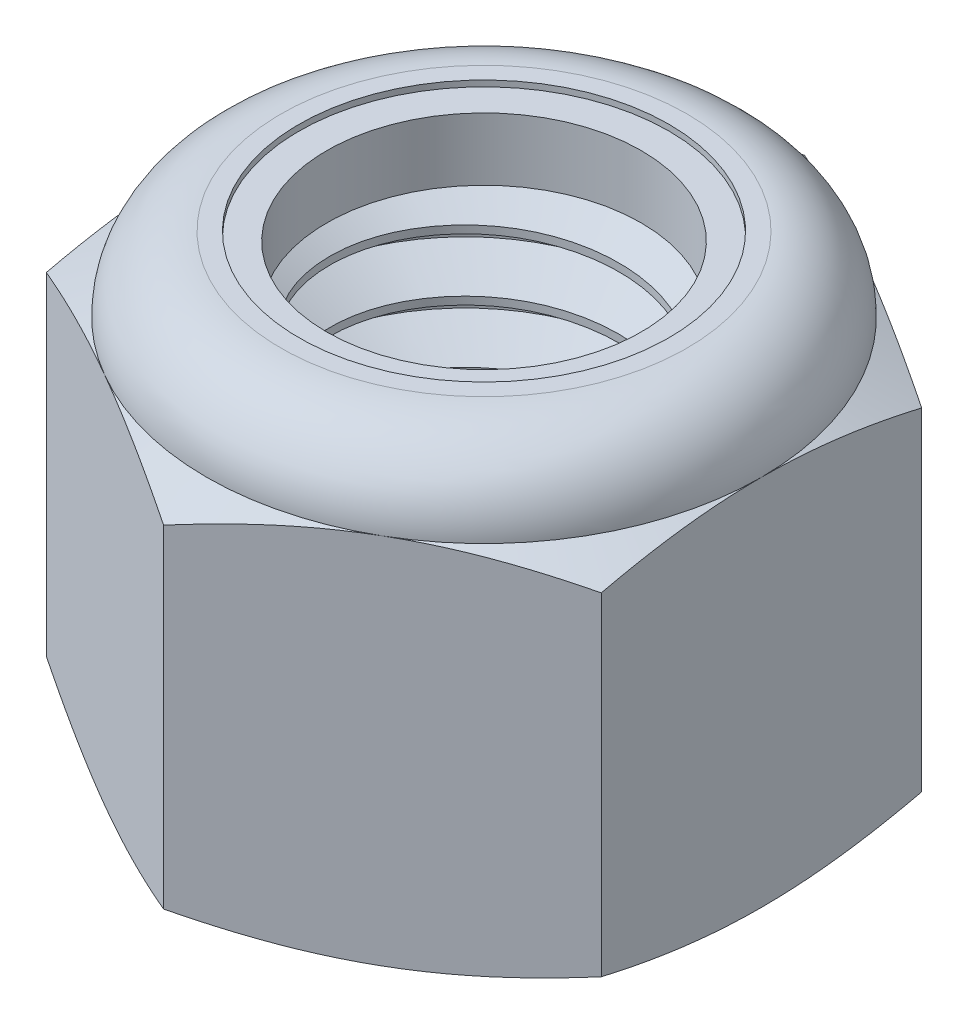
SolidWorks part; units mm, degrees
material "Cast Alloy Steel"
ref_plane "Front" through (0, 0, 0) normal (0, 0, 1) x (1, 0, 0)
ref_plane "Top" through (0, 0, 0) normal (0, 1, 0) x (1, 0, 0)
ref_plane "Right" through (0, 0, 0) normal (1, 0, 0) x (0, 0, -1)
sketch "Sketch1" plane through (0, 0, 0) normal (1, 0, 0) x (0, 0, -1)
  line L0 (0, 0) -> (0, 11.5094) construction
  line L1 (7.1437, 0) -> (-7.1437, 0) construction
  line L2 (-4.7625, 11.5094) -> (4.7625, 11.5094) construction
  line L3 (4.7625, 11.5094) -> (4.7625, 9.9219) construction
  point P9 (-4.7625, 11.5094)
  point P10 (4.7625, 11.5094)
  point P11 (7.1437, 0)
  dimension "Height" = 11.5094
  dimension "Hex Flats" = 14.2875
  dimension "Thread Dia" = 9.525
  dimension "Thread Pitch" = 1.5875
sketch "Sketch13" plane through (0, 0, 0) normal (0, 1, 0) x (1, 0, 0)
  line L1 (0, 8.2489) -> (-7.1438, 4.1244)
  line L2 (-7.1438, 4.1244) -> (-7.1437, -4.1244)
  line L3 (-7.1437, -4.1244) -> (0, -8.2489)
  line L4 (0, -8.2489) -> (7.1438, -4.1244)
  line L5 (7.1438, -4.1244) -> (7.1438, 4.1244)
  line L6 (7.1438, 4.1244) -> (0, 8.2489)
  circle A0 centre (0, 0) radius 7.1437 construction
  circle A1 centre (0, 0) radius 4.7625
  point P11 (0, -4.7625)
  point P13 (0, 4.7625)
extrude "Extrude1" add sketch "Sketch13" along normal up to vertex (11.5094 mm away) up to point (0, 11.5094, 0)
sketch "Sketch5" plane through (0, 0, 0) normal (1, 0, 0) x (0, 0, -1)
  line L0 (0, 0) -> (7.1437, 0)
  line L1 (7.1437, 0) -> (8.2489, 0.5153)
  line L2 (8.2489, 0.5153) -> (8.2489, 9.0758)
  line L3 (8.2489, 9.0758) -> (7.1437, 9.5911)
  line L4 (5.2255, 11.5094) -> (5.2255, 12.7794)
  line L5 (5.2255, 12.7794) -> (9.5189, 12.7794)
  line L6 (9.5189, 12.7794) -> (9.5189, -1.27)
  line L7 (9.5189, -1.27) -> (0, -1.27)
  line L8 (0, -1.27) -> (0, 0)
  line L9 (7.1437, 9.5911) -> (7.1437, 0) construction
  line L12 (8.2489, 11.5094) -> (8.2489, 0) construction
  line L13 (8.2489, 5.7547) -> (9.5189, 5.7547) construction
  line L15 (0, 0) -> (0, 12.7794) construction
  line L18 (7.1437, 0) -> (-7.1437, 0) construction
  line L19 (4.1244, 11.5094) -> (8.2489, 11.5094) construction
  line L20 (0, 12.7794) -> (5.2255, 12.7794) construction
  line L21 (4.1244, 0) -> (8.2489, 0) construction
  arc A0 (7.1437, 9.5911) -> (5.2255, 11.5094) centre (5.2255, 9.5911) ccw
  dimension "D1" = 25
  dimension "D2" = 1.27
  dimension "D4" = 1.9182
revolve "Cut-Revolve3" cut sketch "Sketch5" angle 360 about L15
sketch "Sketch4" plane through (0, 0, 0) normal (1, 0, 0) x (0, 0, -1)
  line L0 (0, 9.5911) -> (5.2388, 9.5911)
  line L1 (5.2388, 9.5911) -> (0, 7.1483)
  line L3 (0, 2.4429) -> (5.2388, 0)
  line L4 (5.2388, 0) -> (0, 0)
  line L5 (0, 0) -> (0, 9.5911) construction
  line L10 (0, 0) -> (0, 11.5094) construction
  line L11 (0, 2.4429) -> (0, 0)
  line L12 (0, 9.5911) -> (0, 7.1483)
  line L13 (6.1867, 9.5911) -> (0, 9.5911) construction
  dimension "D1" = 25
  dimension "D2" = 10.4775
sketch "Sketch6" plane through (0, 0, 0) normal (1, 0, 0) x (0, 0, -1)
  line L0 (0, 9.5911) -> (6.9914, 9.5911)
  line L1 (5.2255, 11.357) -> (2.6128, 11.357)
  line L2 (0, 12.7794) -> (0, 9.5911)
  line L3 (2.6128, 12.7794) -> (0, 12.7794)
  line L4 (0, 12.7794) -> (5.2255, 12.7794) construction
  line L5 (0, 0) -> (0, 12.7794) construction
  line L6 (0, 12.7794) -> (0, 0) construction
  line L7 (2.6128, 11.357) -> (2.6128, 12.7794)
  line L8 (5.2255, 11.5094) -> (5.2255, 11.357) construction
  line L9 (2.6128, 11.357) -> (0, 11.357) construction
  line L10 (0, 11.357) -> (0, 7.1483) construction
  arc A0 (6.9914, 9.5911) -> (5.2255, 11.357) centre (5.2255, 9.5911) ccw
  arc A1 (7.1437, 9.5911) -> (5.2255, 11.5094) centre (5.2255, 9.5911) ccw construction
  dimension "D1" = 0.1524
revolve "Cut-Revolve4" cut sketch "Sketch6" angle 360 about L6
revolve "Cut-Revolve2" cut sketch "Sketch4" angle 360 about L5
sketch "Sketch7" plane through (0, 0, 0) normal (1, 0, 0) x (0, 0, -1)
  line L0 (4.0481, 9.6673) -> (6.9134, 9.6673)
  line L1 (5.2255, 11.2808) -> (4.0481, 11.2808)
  line L2 (4.0481, 11.2808) -> (4.0481, 9.6673)
  line L3 (4.0481, 9.6673) -> (0, 9.6673) construction
  line L4 (0, 9.6673) -> (0, 11.2808) construction
  line L5 (0, 11.2808) -> (4.0481, 11.2808) construction
  line L6 (4.0481, 9.6673) -> (4.0481, 9.5911) construction
  line L7 (0, 9.5911) -> (6.9914, 9.5911) construction
  line L8 (5.2255, 11.2808) -> (5.2255, 11.357) construction
  arc A0 (6.9134, 9.6673) -> (5.2255, 11.2808) centre (5.2255, 9.5911) ccw
  arc A2 (6.9914, 9.5911) -> (5.2255, 11.357) centre (5.2255, 9.5911) ccw construction
  point P15 (4.0481, 11.2808)
  point P18 (-4.6368, 11.2808)
  point P19 (4.6368, 11.2808)
  dimension "D1" = 0.0762
  dimension "D2" = 8.0962
revolve "Revolve2" add sketch "Sketch7" angle 360 about L4
sketch "Sketch2" plane through (0, 0, 0) normal (1, 0, 0) x (0, 0, -1)
  line L0 (-4.7625, 0) -> (-4.7625, 9.5911) construction
  line L1 (0, 0) -> (4.7625, 0)
  line L2 (0, 0) -> (0, 9.5911)
  line L3 (0, 9.5911) -> (4.7625, 9.5911)
  line L4 (4.7625, 0) -> (4.7625, 9.5911)
  line L6 (6.1867, 9.5911) -> (7.1437, 9.5911) construction
  line L7 (0, -4.7625) -> (0, 0) construction
revolve "Revolve1" add sketch "Sketch2" angle 360 about L7
sketch "Sketch9" plane through (0, 0, 0) normal (1, 0, 0) x (0, 0, -1)
  line L0 (4.9344, 11.0794) -> (4.9344, 9.4919) construction
  line L1 (4.9344, 9.4919) -> (3.5595, 10.2857) construction
  line L2 (3.5595, 10.2857) -> (4.9344, 11.0794) construction
  line L3 (3.7314, 10.3849) -> (3.7314, 10.1865) construction
  line L4 (4.7625, 10.9802) -> (4.7625, 9.5911) construction
  line L5 (3.5595, 10.2857) -> (3.7314, 10.2857) construction
  line L6 (4.7625, 10.2857) -> (4.9344, 10.2857) construction
  line L7 (4.8484, 10.2857) -> (4.8484, 11.0298) construction
  line L8 (4.9344, 9.4919) -> (4.8484, 11.0298)
  line L9 (4.8484, 11.0298) -> (3.7314, 10.3849)
  line L10 (3.7314, 10.3849) -> (3.7314, 10.1865)
  line L11 (3.7314, 10.1865) -> (4.9344, 9.4919)
  dimension "D1" = 1.5875
  dimension "D2" = 0.1984
sketch "Sketch10" plane through (0, 9.5911, 0) normal (0, 1, 0) x (1, 0, 0)
  circle A1 centre (0, 0) radius 4.7625
  circle A2 centre (0, 0) radius 4.7625
  dimension "D1" = 0
curve "Helix/Spiral1" pitch 1.5875 height 13.0969 turns 8.25
sweep "Cut-Sweep1" cut profiles "Sketch9" path "Helix/Spiral1"
sketch "Sketch11" plane through (0, 0, 0) normal (1, 0, 0) x (0, 0, -1)
  line L0 (0, 0) -> (0, 11.5094) construction
  line L1 (7.1437, 0) -> (-7.1437, 0) construction
  line L4 (0, 11.5094) -> (0, 0) construction
  line L5 (0, 5.7547) -> (4.7625, 5.7547) construction
  line L6 (0, 0) -> (5.2388, 0)
  line L7 (0, 2.4429) -> (0, 0)
  line L8 (5.2388, 0) -> (0, 2.4429)
  dimension "D1" = 10.4775
  dimension "D2" = 25
revolve "Revolve3" add sketch "Sketch11" angle 360 about L4
sketch "Sketch12" plane through (0, 0, 0) normal (1, 0, 0) x (0, 0, -1)
  line L0 (5.2388, 9.5911) -> (0, 9.5911)
  line L1 (0, 9.5911) -> (0, 0)
  line L2 (0, 0) -> (5.2388, 0)
  line L3 (7.1437, 0) -> (-7.1437, 0) construction
  line L4 (5.2388, 0) -> (5.2388, 9.5911)
  line L5 (-5.2388, 0) -> (5.2388, 0) construction
revolve "Revolve4" add sketch "Sketch12" angle 360 about L0
combine bodies "Combine1" bodies to combine 136 133
equation "\"D4@Sketch5\" = \"Height@Sketch1\" / 6"
equation "\"D1@Sketch9\" = \"Thread Pitch@Sketch1\""
equation "\"D2@Sketch9\" = \"Thread Pitch@Sketch1\" / 8"
equation "\"D4@Helix/Spiral1\" = \"Thread Pitch@Sketch1\""
equation "\"D3@Helix/Spiral1\" = \"Thread Pitch@Sketch1\" + \"Height@Sketch1\""
equation "\"D2@Sketch4\" = \"Thread Dia@Sketch1\" * 1.1"
equation "\"D1@Sketch11\" = \"Thread Dia@Sketch1\" * 1.1"
equation "\"D2@Sketch7\" = \"Thread Dia@Sketch1\" * .85"
